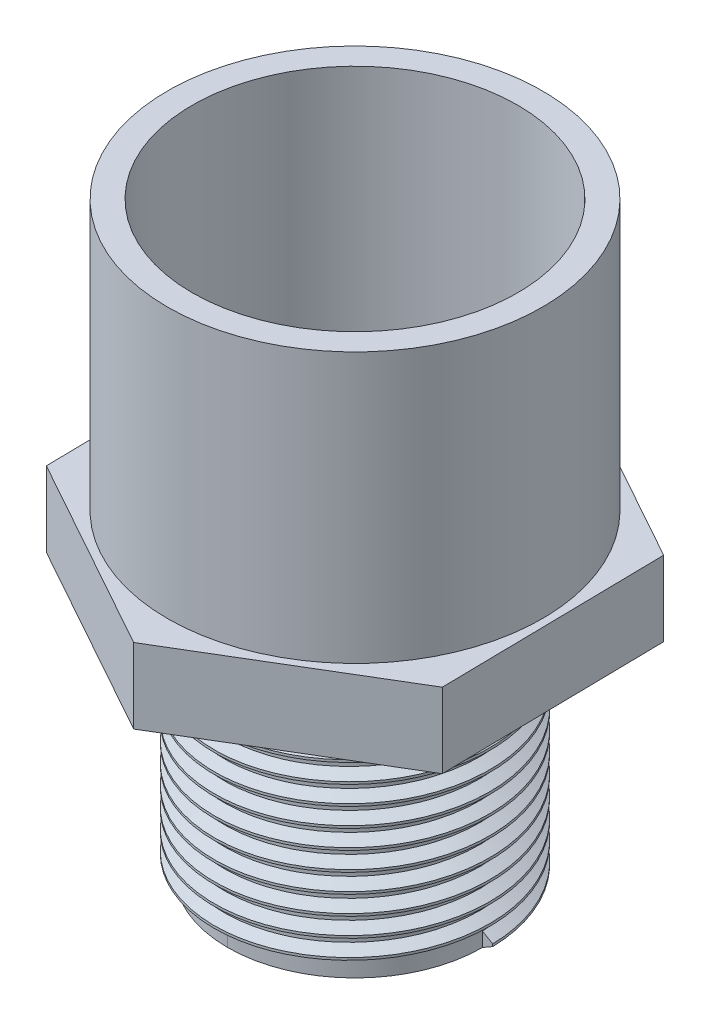
SolidWorks part; units mm, degrees
ref_plane "Front Plane" through (0, 0, 0) normal (0, 0, 1) x (1, 0, 0)
ref_plane "Top Plane" through (0, 0, 0) normal (0, 1, 0) x (1, 0, 0)
ref_plane "Right Plane" through (0, 0, 0) normal (1, 0, 0) x (0, 0, -1)
sketch "Sketch1" plane through (0, 0, 0) normal (0, 1, 0) x (1, 0, 0)
  line L1 (13.1194, -7.2948) -> (12.8772, 7.7143)
  line L2 (12.8772, 7.7143) -> (-0.2422, 15.0092)
  line L3 (-0.2422, 15.0092) -> (-13.1194, 7.2948)
  line L4 (-13.1194, 7.2948) -> (-12.8772, -7.7143)
  line L5 (-12.8772, -7.7143) -> (0.2422, -15.0092)
  line L6 (0.2422, -15.0092) -> (13.1194, -7.2948)
  circle A0 centre (0, 0) radius 12.5
  circle A1 centre (0, 0) radius 8.5
  circle A2 centre (0, 0) radius 13 construction
  circle A3 centre (0, 0) radius 10.85
  dimension "D1" = 26
  dimension "D2" = 25
  dimension "D3" = 17
  dimension "D4" = 21.7
extrude "Boss-Extrude1" add sketch "Sketch1" along normal blind 18 contours A0 A1 region at (-12.1464, 0, 0)
extrude "Boss-Extrude2" add sketch "Sketch1<3>" against normal blind 5 separate body contours L5 L6 L1 L2 L3 L4 A0 | A0 region at (6.4759, 0, 10.81)
sketch "Sketch1<3>" plane through (0, 0, 0) normal (0, 1, 0) x (1, 0, 0) same geometry as "Sketch1"
extrude "Boss-Extrude3" add sketch "Sketch1<4>" against normal blind 21 separate body contours A1 region at (0, 0, 0)
sketch "Sketch1<4>" plane through (0, 0, 0) normal (0, 1, 0) x (1, 0, 0) same geometry as "Sketch1"
sketch "Sketch2" plane through (0, -21, 0) normal (0, -1, 0) x (1, 0, 0)
  circle A0 centre (0, 0) radius 6.75
  dimension "D1" = 13.5
extrude "Cut-Extrude1" cut sketch "Sketch2" against normal through all
thread "Thread1" pitch 1.27 method extrude profile "Thread Profile2" start angle 0, offset 0, length 0, pitch 1.27, diameter 17
ref_plane "Plane2" through (8.5, -21, 0) normal (0, 0, 1) x (1, 0, 0)
sketch "Thread Profile2" plane through (8.5, -21, 0) normal (0, 0, 1) x (1, 0, 0)
  line L0 (0, 0) -> (0, 1.27) construction
  line L1 (0, 0) -> (0.6874, 0.3969)
  line L2 (0.6874, 0.3969) -> (0.6874, 0.5556)
  line L3 (0.6874, 0.5556) -> (0, 0.9525)
  line L4 (0.6874, 0.4762) -> (0, 0.4762) construction
  line L11 (0, 0) -> (0, 0.9525)
  point P2 (0, 0)
  dimension "Pitch" = 1.27
  dimension "Profile_Angle" = 60
  dimension "Profile_Land" = 0.1588
  dimension "Profile_Height" = 0.6874
